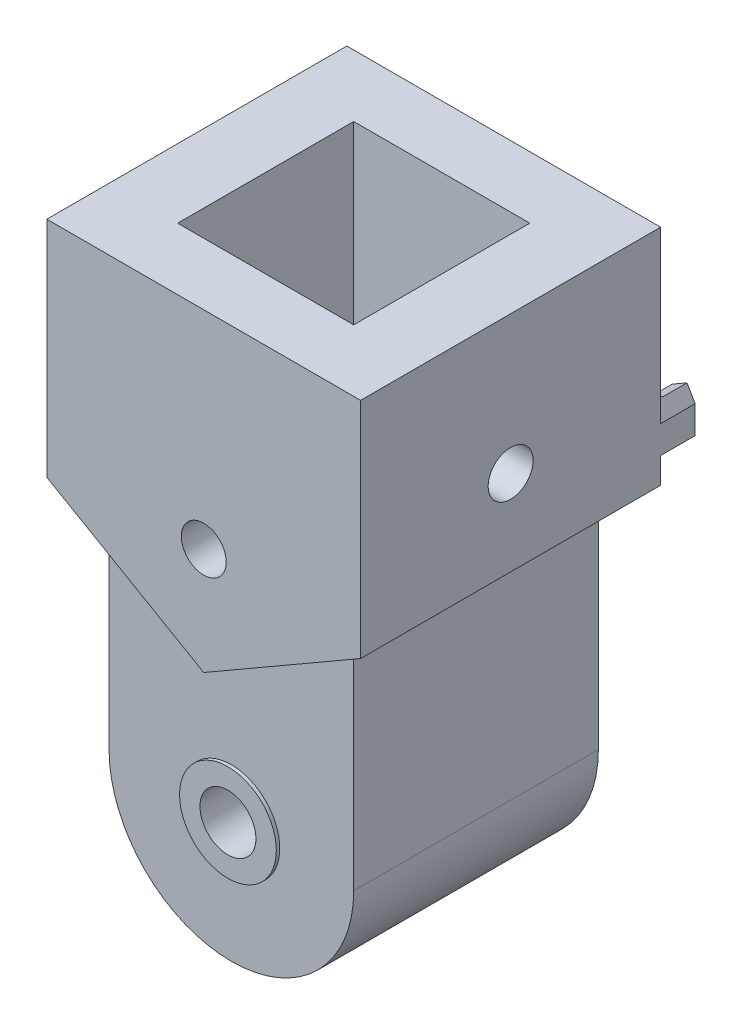
SolidWorks part; units mm, degrees
material "PETG"
ref_plane "Front Plane" through (0, 0, 0) normal (0, 0, 1) x (1, 0, 0)
ref_plane "Top Plane" through (0, 0, 0) normal (0, 1, 0) x (1, 0, 0)
ref_plane "Right Plane" through (0, 0, 0) normal (1, 0, 0) x (0, 0, -1)
sketch "Sketch1" plane through (0, 0, 0) normal (0, 1, 0) x (1, 0, 0)
  line L1 (-12.7375, -12.7375) -> (12.7375, -12.7375)
  line L2 (-12.7375, -12.7375) -> (-12.7375, 12.7375)
  line L3 (-12.7375, 12.7375) -> (12.7375, 12.7375)
  line L4 (12.7375, -12.7375) -> (12.7375, 12.7375)
  line L5 (-17.7, -17.7) -> (17.7, -17.7)
  line L6 (-17.7, -17.7) -> (-17.7, 17.7)
  line L7 (-17.7, 17.7) -> (17.7, 17.7)
  line L8 (17.7, -17.7) -> (17.7, 17.7)
  point P8 (0, -17.7)
  point P9 (0, -12.7375)
  point P12 (-17.7, 0)
  point P13 (-12.7375, 0)
  dimension "D1" = 25.475
  dimension "D2" = 35.4
extrude "Boss-Extrude1" add sketch "Sketch1" along normal blind 50.0375
extrude "Boss-Extrude2" add sketch "Sketch1<3>" against normal blind 9.9625 contours L1 L4 L3 L2 | L5 L8 L7 L6 L4 L1 L2 L3 region at (0, 0, 0) region at (-17.1994, 0, 0)
sketch "Sketch1<3>" plane through (0, 0, 0) normal (0, 1, 0) x (1, 0, 0) same geometry as "Sketch1"
sketch "Sketch2" plane through (0, 0, -17.7) normal (0, 0, 1) x (1, 0, 0)
  line L1 (17.7, 50.0375) -> (17.7, -9.9625) construction
  line L4 (-17.7, -9.9625) -> (17.7, -9.9625) construction
  line L5 (-17.7, -15.9125) -> (-17.7, -9.9625)
  line L6 (17.7, -9.9625) -> (17.7, -15.9125)
  line L7 (17.7, -9.9625) -> (-17.7, -9.9625)
  circle A0 centre (0, -15.9625) radius 4.05
  circle A2 centre (0, -15.9625) radius 11 construction
  arc A3 (17.7, -15.9125) -> (-17.7, -15.9125) centre (0, -15.9125) cw
  dimension "D1" = 8.1
  dimension "D3" = 22
  dimension "D2" = 6
  dimension "D4" = 5.95
extrude "Boss-Extrude5" add sketch "Sketch2" along normal up to surface (35.4 mm away) up to face at (0, 20.0375, 17.7)
ref_plane "Plane1" through (0, -33.6125, 0) normal (0, -1, 0) x (-1, 0, 0)
sketch "Sketch3" plane through (0, -33.6125, 0) normal (0, -1, 0) x (-1, 0, 0)
  circle A0 centre (0, 0) radius 3.15
  dimension "D1" = 6.3
extrude "Cut-Extrude1" cut sketch "Sketch3" against normal through all
sketch "Sketch4" plane through (0, -33.6125, 0) normal (0, -1, 0) x (-1, 0, 0)
  circle A0 centre (0, 0) radius 5.5
  dimension "D1" = 11
extrude "Cut-Extrude2" cut sketch "Sketch4" against normal offset from surface (25.6125 mm away) 8 up to face at (0, 0, 3.15)
sketch "Sketch5" plane through (0, 0, 17.7) normal (0, 0, 1) x (1, 0, 0)
  circle A0 centre (0, -15.9625) radius 7
  circle A1 centre (0, -15.9625) radius 4.05 construction
  circle M6 centre (0, -15.9625) radius 4.05
  dimension "D1" = 14
extrude "Boss-Extrude6" add sketch "Sketch5" along normal blind 0.5 contours A0 M6 region at (-6.802, -15.9625, 17.7)
mirror "Mirror1" about plane through (0, 0, 0) normal (0, 0, 1) of "Boss-Extrude6"
sketch "Sketch6" plane through (0, 0, 17.7) normal (0, 0, 1) x (1, 0, 0)
  line L5 (8.875, -31.2845) -> (52.1763, -6.2845) construction
  line L6 (-8.875, -0.5405) -> (34.4263, 24.4595) construction
  line L7 (52.1763, -6.2845) -> (34.4263, 24.4595) construction
  line L8 (0, -16) -> (0, -79.4793) construction
  line L9 (17.7, 50.0375) -> (17.7, -15.9125) construction
  line L10 (17.7, 14.8025) -> (-17.7, 14.8025)
  line L11 (17.7, 14.8025) -> (17.7, 50.0375)
  line L12 (17.7, 50.0375) -> (-17.7, 50.0375)
  line L13 (-17.7, 14.8025) -> (-17.7, 50.0375)
  line L14 (17.7, 14.8025) -> (0, 4.5834)
  line L15 (0, 4.5834) -> (-17.7, 14.8025)
  circle A1 centre (0, -15.9125) radius 17.75
  arc A2 (-17.7, -15.9125) -> (17.7, -15.9125) centre (0, -15.9125) ccw construction
  line M4 (-17.7, 50.0375) -> (-17.7, -15.9125)
  line M6 (17.7, -15.9125) -> (17.7, 50.0375)
  line M7 (17.7, 50.0375) -> (-17.7, 50.0375)
  dimension "D1" = 50
  dimension "D2" = 120
  dimension "D3" = 35.5
extrude "Boss-Extrude7" add sketch "Sketch6" along normal blind 4 contours L14 L10 M4 | L10 M6 M7 M4 region at (0, 11.3962, 17.7) region at (0, 32.42, 17.7)
sketch "Sketch7" plane through (0, 0, 21.7) normal (0, 0, 1) x (1, 0, 0)
  line L0 (17.7, 50.0375) -> (-17.7, 50.0375) construction
  line L1 (17.7, 20.0375) -> (0, 20.0375) construction
  line L2 (17.7, 14.8025) -> (17.7, 50.0375) construction
  line L3 (0, 20.0375) -> (-17.7, 20.0375) construction
  line L4 (-17.7, 50.0375) -> (-17.7, 14.8025) construction
  circle A0 centre (0, 20.0375) radius 3.25
  dimension "D1" = 30
  dimension "D2" = 6.5
extrude "Cut-Extrude3" cut sketch "Sketch7" against normal up to next
mirror "Mirror2" about plane through (0, 0, 0) normal (0, 0, 1) of "Boss-Extrude7", "Cut-Extrude3"
sketch "Sketch9" plane through (0, 0, 0) normal (0, 0, 1) x (1, 0, 0)
  line L0 (-17.7, 14.8025) -> (-22.7, 17.6893)
  line L1 (0, 4.5834) -> (-17.7, 14.8025) construction
  line L3 (-17.7, 14.8025) -> (-17.7, 50.0375)
  line L4 (-17.7, 50.0375) -> (-22.7, 50.0375)
  line L5 (-22.7, 17.6893) -> (-22.7, 50.0375)
  line L6 (0, 0) -> (0, 50000) construction
  line L7 (22.7, 17.6893) -> (22.7, 50.0375)
  line L8 (17.7, 50.0375) -> (22.7, 50.0375)
  line L9 (17.7, 14.8025) -> (17.7, 50.0375)
  line L10 (17.7, 14.8025) -> (22.7, 17.6893)
  dimension "D1" = 5
extrude "Boss-Extrude9" add sketch "Sketch9" along normal up to surface and the other way up to surface up to face at (3.25, 20.0375, 21.7) other way up to face at (3.25, 20.0375, -21.7)
sketch "Sketch10" plane through (0, 0, 0) normal (-1, 0, 0) x (0, 0, 1)
  line L0 (21.7, 50.0375) -> (-21.7, 50.0375) construction
  circle A0 centre (0, 30.0375) radius 3.25
  dimension "D1" = 6.5
  dimension "D2" = 20
extrude "Cut-Extrude4" cut sketch "Sketch10" against normal through all both and the other way through all
sketch "Sketch11" plane through (0, 0, -21.7) normal (0, 0, -1) x (-1, 0, 0)
  line L0 (-12.9904, 12.0834) -> (-24.3137, 18.6209)
  line L1 (-12.9904, 12.0834) -> (-9.4716, 18.1781)
  line L2 (-24.3137, 18.6209) -> (-20.7949, 24.7156)
  line L3 (-9.4716, 18.1781) -> (-20.7949, 24.7156)
  line L4 (-22.7, 17.6893) -> (0, 4.5834) construction
  line L5 (-12.9904, 12.0834) -> (-11.2583, 11.0834)
  line L6 (-11.2583, 11.0834) -> (-6.7396, 18.9101)
  line L7 (-6.7396, 18.9101) -> (-8.9046, 20.1601)
  line L8 (-8.9046, 20.1601) -> (-9.9046, 18.4281)
  line L9 (-12.9904, 12.0834) -> (-11.2583, 11.0834)
  line L10 (-20.3619, 24.4656) -> (-19.3619, 26.1976)
  line L11 (-19.3619, 26.1976) -> (-21.527, 27.4476)
  line L12 (-21.527, 27.4476) -> (-22.7, 25.4159)
  line L13 (-22.7, 17.6893) -> (-22.7, 50.0375) construction
  line L14 (-22.7, 25.4159) -> (-22.7, 21.4159)
  line L15 (-18.5974, 23.4468) -> (-16.8653, 22.4468)
  line L16 (-18.5974, 23.4468) -> (-17.5974, 25.1789)
  line L17 (-16.8653, 22.4468) -> (-15.8653, 24.1789)
  line L18 (-17.5974, 25.1789) -> (-15.8653, 24.1789)
  line L19 (-13.4012, 20.4468) -> (-11.6692, 19.4468)
  line L20 (-13.4012, 20.4468) -> (-12.4012, 22.1789)
  line L21 (-11.6692, 19.4468) -> (-10.6692, 21.1789)
  line L22 (-12.4012, 22.1789) -> (-10.6692, 21.1789)
  line L23 (-11.1692, 20.3129) -> (-9.4046, 19.2941) construction
  line L24 (-19.8619, 25.3316) -> (-18.0974, 24.3129) construction
  line L25 (-19.3619, 26.1976) -> (-8.9046, 20.1601)
  point P4 (0, 4.5834)
  point P19 (-16.7313, 24.6789)
  point P30 (-11.5352, 21.6789)
  line M19 (-22.7, 50.0375) -> (-22.7, 17.6893)
  line M20 (-22.7, 17.6893) -> (0, 4.5834)
  dimension "D1" = 13.075
  dimension "D2" = 7.0375
  dimension "D3" = 15
  dimension "D4" = 2
  dimension "D5" = 0.5
  dimension "D6" = 0.5
  dimension "D7" = 2
  dimension "D8" = 2
  dimension "D9" = 6
extrude "Boss-Extrude10" add sketch "Sketch11" along normal blind 5 contours L11 L12 L2 L3 L10 M19 | L7 L8 L3 L1 L6 M20 region at (9.8295, 15.6893, -21.7) region at (21.4509, 25.0541, -21.7)
extrude "Boss-Extrude11" add sketch "Sketch11<3>" along normal blind 1.5 contours L25 L17 L3 L20 | L18 L16 L3 L17 | L25 L10 L3 L16 | L22 L20 L3 L21 | L25 L21 L3 L8 region at (10.2869, 19.8035, -21.7) region at (12.0352, 20.8129, -21.7) region at (18.9796, 24.8222, -21.7) region at (14.6333, 22.3129, -21.7) region at (17.2313, 23.8129, -21.7)
sketch "Sketch11<3>" plane through (0, 0, -21.7) normal (0, 0, -1) x (-1, 0, 0) same geometry as "Sketch11"
chamfer "Chamfer1" distance 1.5 angle 45 1 edges at (14.1333, 23.1789, -21.7)
mirror "Mirror3" about plane through (0, 0, 0) normal (1, 0, 0) of "Boss-Extrude11", "Chamfer1", "Boss-Extrude10"
equation "\"tol_dia_id_intfc\" = 0.0500mm ' For hole diameters - Interference fit"
equation "\"tol_dia_id_slip\"  = 0.0750mm ' For hole diameters - Slip fit"
equation "\"tol_dia_id_clear\" = 0.1000mm ' For hole diameters - Clearance fit"
equation "\"tol_dia_od_intfc\" = 0.0500mm ' For shaft diameters - Interference fit"
equation "\"tol_dia_od_slip\"  = 0.0750mm ' For shaft diameters - Slip fit"
equation "\"tol_dia_od_clear\" = 0.1000mm ' For shaft diameters - Clearance fit"
equation "\"tol_general_intfc\"= 0.0250mm ' For general parts (Horiz) - Interference fit"
equation "\"tol_general_slip\" = 0.0375mm ' For general parts (Horiz) - Slip fit"
equation "\"tol_general_clear\"= 0.0500mm ' For general parts (Horiz) - Clearance fit"
equation "\"tol_layer_intfc\"  = 0.0250mm ' For all parts (Vert) - Interference fit"
equation "\"tol_layer_slip\"   = 0.0375mm ' For all parts (Vert) - Slip fit"
equation "\"tol_layer_clear\"  = 0.0500mm ' For all parts (Vert) - Clearance fit"
equation "\"tol_corner_rad\"   = 0.100mm ' For corners that fit into other parts"
equation "\"D1@Sketch1\"=25.40mm+\"tol_general_slip\"*2"
equation "\"D2@Sketch1\"=25.4+10"
equation "\"D1@Boss-Extrude1\"= 50.00mm + \"tol_layer_slip\""
equation "\"D1@Boss-Extrude2\"=10.00mm-\"tol_layer_slip\""
equation "\"D1@Sketch2\"=8.00mm+\"tol_dia_id_clear\""
equation "\"D4@Sketch2\"=6.00mm-\"tol_dia_od_clear\"/2"
equation "\"D3@Sketch6\"=25.4+10+\"tol_general_clear\"*2"
equation "\"D1@Sketch11\"=13mm+\"tol_general_slip\"*2"
equation "\"D2@Sketch11\"=7mm+\"tol_general_slip\""
equation "\"D6@Sketch11\"=\"D5@Sketch11\""
equation "\"D8@Sketch11\"=\"D7@Sketch11\""
